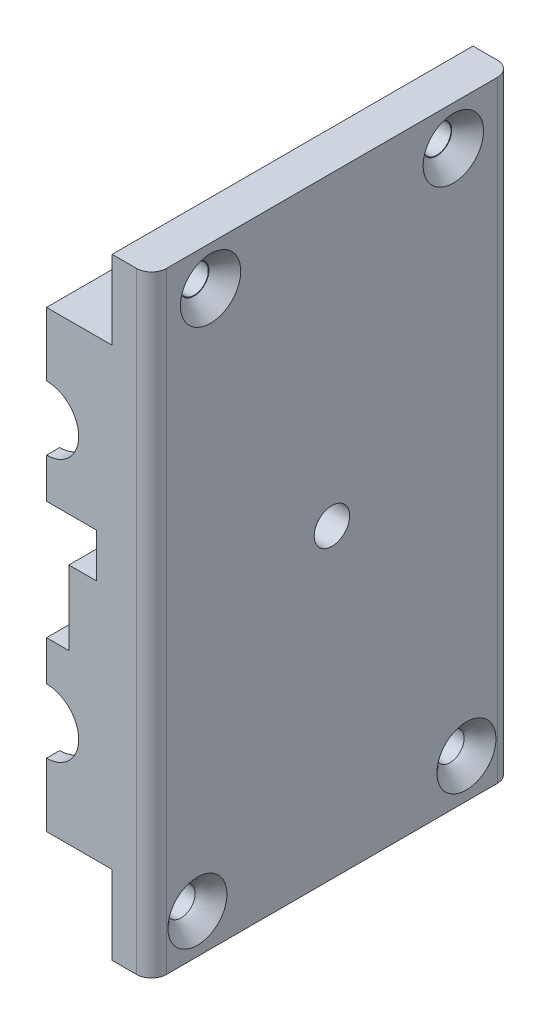
SolidWorks part; units mm, degrees
ref_plane "Front Plane" through (0, 0, 0) normal (0, 0, 1) x (1, 0, 0)
ref_plane "Top Plane" through (0, 0, 0) normal (0, 1, 0) x (1, 0, 0)
ref_plane "Right Plane" through (0, 0, 0) normal (1, 0, 0) x (0, 0, -1)
sketch "Sketch1" plane through (0, 0, 0) normal (0, 0, 1) x (1, 0, 0)
  line L0 (0, 0) -> (0, -93.2)
  line L1 (0, -93.2) -> (-6, -93.2)
  line L2 (-6, -93.2) -> (-6, -81.2)
  line L3 (-6, -81.2) -> (-16, -81.2)
  line L4 (-16, -81.2) -> (-16, -74.2)
  line L5 (-16, -59) -> (-16, -44.3)
  line L6 (-16, -44.3) -> (-8.4, -44.3)
  line L7 (-8.4, -44.3) -> (-8.4, -37.6)
  line L8 (-8.4, -37.6) -> (-16, -37.6)
  line L9 (-16, -37.6) -> (-16, -34.2)
  line L10 (-16, -19) -> (-16, -12)
  line L11 (-16, -12) -> (-6, -12)
  line L12 (-6, -12) -> (-6, 0)
  line L13 (-6, 0) -> (0, 0)
  arc A0 (-16, -74.2) -> (-16, -59) centre (-16, -66.6) ccw
  arc A1 (-16, -34.2) -> (-16, -19) centre (-16, -26.6) ccw
  dimension "D6" = 7.6
  dimension "D7" = 7.6
  dimension "D1" = 6
  dimension "D2" = 12
  dimension "D3" = 12
  dimension "D4" = 14.7
  dimension "D5" = 40
  dimension "D8" = 7
  dimension "D9" = 3.4
  dimension "D11" = 10
  dimension "D12" = 10
extrude "Boss-Extrude1" add sketch "Sketch1" along normal blind 55
ref_plane "Plane1" through (0, 0, 28.5) normal (0, 0, -1) x (-1, 0, 0)
sketch "Sketch2" plane through (0, 0, 28.5) normal (0, 0, -1) x (-1, 0, 0)
  line L0 (16, -34.2) -> (16, -31.5)
  line L1 (16, -21.7) -> (16, -19)
  arc A0 (16, -19) -> (16, -34.2) centre (16, -26.6) ccw
  arc A1 (16, -21.7) -> (16, -31.5) centre (16, -26.6) ccw
  dimension "D1" = 4.9
extrude "Boss-Extrude2" add sketch "Sketch2" along normal blind 2
sketch "Sketch3" plane through (0, 0, 28.5) normal (0, 0, -1) x (-1, 0, 0)
  line L0 (16, -74.2) -> (16, -71.5)
  line L1 (16, -61.7) -> (16, -59)
  arc A0 (16, -59) -> (16, -74.2) centre (16, -66.6) ccw
  arc A1 (16, -61.7) -> (16, -71.5) centre (16, -66.6) ccw
  dimension "D1" = 4.9
extrude "Boss-Extrude3" add sketch "Sketch3" along normal blind 2
ref_plane "Plane2" through (0, 0, 2) normal (0, 0, -1) x (-1, 0, 0)
sketch "Sketch4" plane through (0, 0, 2) normal (0, 0, -1) x (-1, 0, 0)
  line L1 (16, -59) -> (16, -61.7)
  line L2 (16, -74.2) -> (16, -81.2) construction
  line L4 (16, -71.5) -> (16, -74.2)
  line L5 (16, -19) -> (16, -21.7)
  line L6 (16, -31.5) -> (16, -34.2)
  arc A1 (16, -59) -> (16, -74.2) centre (16, -66.6) ccw construction
  arc A2 (16, -74.2) -> (16, -59) centre (16, -66.6) cw
  arc A4 (16, -61.7) -> (16, -71.5) centre (16, -66.6) ccw
  arc A5 (16, -34.2) -> (16, -19) centre (16, -26.6) cw
  arc A6 (16, -21.7) -> (16, -31.5) centre (16, -26.6) ccw
  dimension "D1" = 4.9
  dimension "D2" = 4.9
extrude "Boss-Extrude5" add sketch "Sketch4" along normal blind 2
ref_plane "Plane3" through (0, 0, 53) normal (0, 0, -1) x (-1, 0, 0)
sketch "Sketch5" plane through (0, 0, 53) normal (0, 0, -1) x (-1, 0, 0)
  line L0 (16, -19) -> (16, -21.7)
  line L1 (16, -31.5) -> (16, -34.2)
  line L2 (16, -59) -> (16, -61.7)
  line L3 (16, -71.5) -> (16, -74.2)
  arc A0 (16, -19) -> (16, -34.2) centre (16, -26.6) ccw construction
  arc A1 (16, -34.2) -> (16, -19) centre (16, -26.6) cw
  arc A2 (16, -21.7) -> (16, -31.5) centre (16, -26.6) ccw
  arc A3 (16, -74.2) -> (16, -59) centre (16, -66.6) cw
  arc A4 (16, -61.7) -> (16, -71.5) centre (16, -66.6) ccw
  dimension "D1" = 4.9
extrude "Boss-Extrude6" add sketch "Sketch5" against normal blind 2
sketch "Sketch7" plane through (0, 0, 55) normal (0, 0, 1) x (1, 0, 0)
  line L1 (-16, -44.3) -> (-12.6, -44.3)
  line L2 (-16, -44.3) -> (-16, -55.6)
  line L3 (-16, -55.6) -> (-12.6, -55.6)
  line L4 (-12.6, -44.3) -> (-12.6, -55.6)
  dimension "D1" = 3.4
  dimension "D2" = 11.3
extrude "Cut-Extrude2" cut sketch "Sketch7" against normal up to surface (55 mm away) up to face at (-9.9375, -45.1875, 0)
sketch "Sketch8" plane through (0, 0, 0) normal (1, 0, 0) x (0, 0, -1)
  line L0 (-55, -93.2) -> (-55, 0) construction
  line L1 (0, -93.2) -> (0, 0) construction
  line L2 (-55, 0) -> (0, 0) construction
  line L3 (-55, -93.2) -> (0, -93.2) construction
  circle A0 centre (-46, -6) radius 2.15
  circle A1 centre (-9, -6) radius 2.15
  circle A2 centre (-7, -87.2) radius 2.15
  circle A3 centre (-48, -87.2) radius 2.15
  dimension "D1" = 4.3
  dimension "D2" = 4.3
  dimension "D3" = 4.3
  dimension "D4" = 4.3
  dimension "D5" = 9
  dimension "D6" = 9
  dimension "D7" = 7
  dimension "D8" = 7
  dimension "D9" = 6
  dimension "D10" = 6
  dimension "D11" = 6
  dimension "D12" = 6
extrude "Cut-Extrude3" cut sketch "Sketch8" against normal up to surface (6 mm away) up to face at (-6, -6, 27.5)
sketch "Sketch9" plane through (0, 0, 0) normal (1, 0, 0) x (0, 0, -1)
  line L0 (-55, 0) -> (0, 0) construction
  line L1 (-55, -93.2) -> (-55, 0) construction
  circle A0 centre (-27.5, -46.6) radius 2.7
  dimension "D1" = 5.4
  dimension "D2" = 46.6
  dimension "D3" = 27.5
extrude "Cut-Extrude4" cut sketch "Sketch9" against normal up to surface (12.6 mm away) up to face at (-12.6, -49.95, 27.5)
ref_plane "Plane4" through (-2.5, 0, 0) normal (1, 0, 0) x (0, 0, -1)
sketch "Sketch12" plane through (-2.5, 0, 0) normal (1, 0, 0) x (0, 0, -1)
  circle A0 centre (-46, -6) radius 2.15 construction
  circle A1 centre (-46, -6) radius 2.25
  circle A2 centre (-46, -6) radius 2.15 construction
  point P1 (0, 0)
  point P6 (0, 0)
  dimension "D1" = 4.5
sketch "Sketch13" plane through (0, 0, 0) normal (1, 0, 0) x (0, 0, -1)
  circle A0 centre (-46, -6) radius 4.6
  dimension "D1" = 9.2
loft "Cut-Loft1" cut profiles "Sketch13", "Sketch12" connector at (0, -8.7689, 49.6733) connector at (-2.5, -7.7735, 47.3846)
pattern_linear "LPattern1" count 2 spacing 37 along (0, 0, -1) of "Cut-Loft1"
sketch "Sketch14" plane through (-2.5, 0, 0) normal (1, 0, 0) x (0, 0, -1)
  circle A0 centre (-48, -87.2) radius 2.15 construction
  circle A1 centre (-48, -87.2) radius 2.15
sketch "Sketch15" plane through (0, 0, 0) normal (1, 0, 0) x (0, 0, -1)
  circle A0 centre (-48, -87.2) radius 4.5
  dimension "D1" = 9
loft "Cut-Loft2" cut profiles "Sketch14", "Sketch15" connector at (-2.5, -88.8038, 46.5681) connector at (0, -88.245, 43.623)
pattern_linear "LPattern2" count 2 spacing 41 along (0, 0, -1) of "Cut-Loft2"
fillet "Fillet1" radius 2.3 2 edges at (0, -46.6, 0) (0, -46.6, 55)
